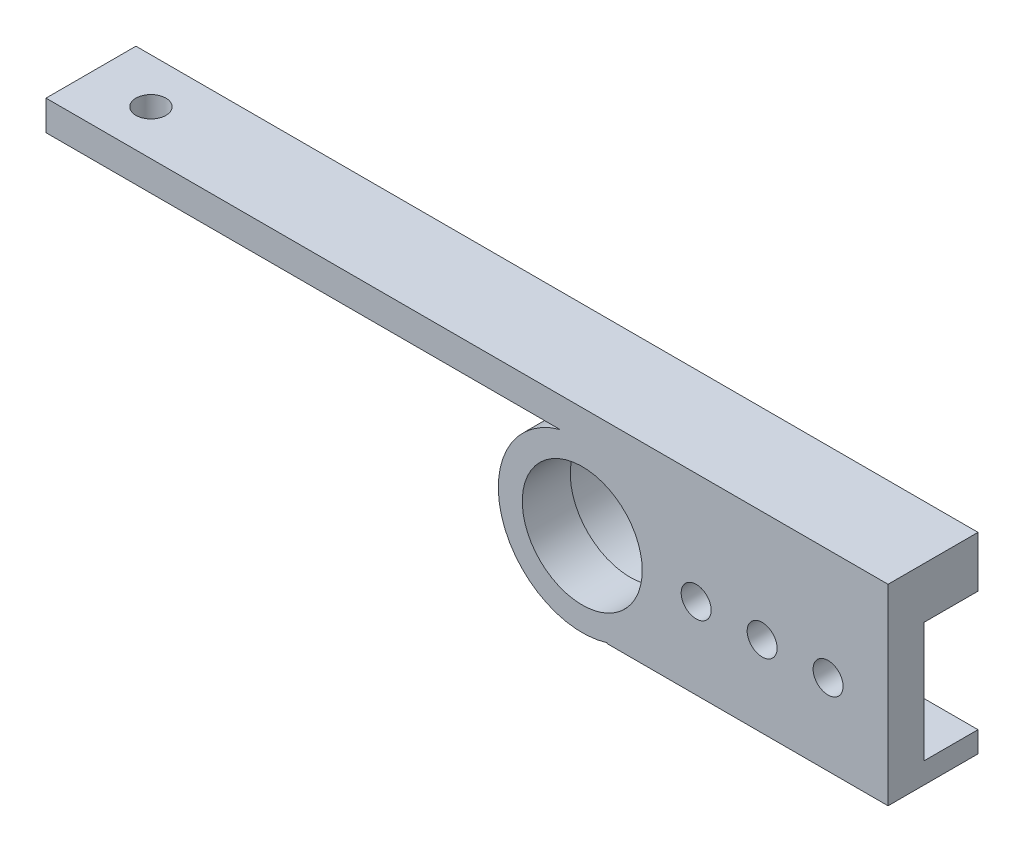
SolidWorks part; units mm, degrees
ref_plane "前视基准面" through (0, 0, 0) normal (0, 0, 1) x (1, 0, 0)
ref_plane "上视基准面" through (0, 0, 0) normal (0, 1, 0) x (1, 0, 0)
ref_plane "右视基准面" through (0, 0, 0) normal (1, 0, 0) x (0, 0, -1)
sketch "草图1" plane through (0, 0, 0) normal (0, 0, 1) x (1, 0, 0)
  line L1 (20, -10) -> (-20, -10)
  line L2 (20, -10) -> (20, 10)
  line L3 (20, 10) -> (-20, 10)
  line L4 (-20, -10) -> (-20, 10)
  line L5 (20, -10) -> (-20, 10) construction
  line L6 (20, 10) -> (-20, -10) construction
  point P0 (0, 0)
  dimension "D1" = 40
  dimension "D2" = 20
extrude "凸台-拉伸1" add sketch "草图1" along normal blind 6
sketch "草图2" plane through (0, 0, 6) normal (0, 0, 1) x (1, 0, 0)
  line L0 (20, -10) -> (20, 10) construction
  circle A0 centre (10, 0) radius 2.5
  circle A1 centre (-1, 0) radius 2.5
  circle A2 centre (-12, 0) radius 2.5
  dimension "D1" = 10
  dimension "D2" = 5
  dimension "D3" = 3
extrude "切除-拉伸1" cut sketch "草图2" against normal through all
sketch "草图3" plane through (0, 0, 6) normal (0, 0, 1) x (1, 0, 0)
  line L0 (20, 13.5) -> (20, 10)
  line L1 (20, -13.5) -> (-26.894, -13.5)
  line L3 (20, 13.5) -> (-26.894, 13.5)
  line L4 (-20, 10) -> (-20, -10)
  line L5 (-20, -10) -> (20, -10)
  line L6 (20, -10) -> (20, 10)
  line L7 (20, 10) -> (-20, 10)
  line L8 (-20, 10) -> (-20, -10)
  line L9 (-20, -10) -> (20, -10)
  line L10 (20, -10) -> (20, 10)
  line L11 (20, 10) -> (-20, 10)
  line L12 (-26.894, -13.5) -> (-26.894, 13.5)
  line L13 (20, -10.0394) -> (-26.894, 13.5) construction
  line L14 (20, 10.0394) -> (-26.894, -13.5) construction
  line L15 (20, -10) -> (20, -13.5)
  circle A0 centre (-31, 0) radius 11
  circle A1 centre (-31, 0) radius 14
  point P2 (0, 0)
  line M10 (-20, 10) -> (-20, -10)
  line M11 (-20, -10) -> (20, -10)
  line M13 (20, 10) -> (-20, 10)
  dimension "D3" = 22
  dimension "D4" = 28
  dimension "D2" = 3.5
  dimension "D1" = 0
extrude "凸台-拉伸2" add sketch "草图3" against normal blind 15 contours L3 A1 L1 L12 A0 | A1 L1 L15 M11 M10 | L1 A1 L8 A0 L12 | L8 A1 L3 L12 A0 | L8 A1 | A1 L0 L3 M10 M13 region at (-1.9449, 11.7771, 6) region at (-1.9449, -11.7771, 6) region at (-23.0173, 9.0328, 6) region at (-27.2274, 11.7946, 6) region at (-18.7882, 0, 6) region at (-23.0173, -9.0328, 6)
sketch "草图5" plane through (0, 0, 6) normal (0, 0, 1) x (1, 0, 0)
  circle A0 centre (-31, 0) radius 10
  circle A1 centre (-31, 0) radius 11 construction
  circle A2 centre (-31, 0) radius 11
  dimension "D1" = 20
extrude "凸台-拉伸3" add sketch "草图5" against normal blind 8
sketch "草图6" plane through (0, 0, 6) normal (0, 0, 1) x (1, 0, 0)
  circle A0 centre (-31, 0) radius 8.5
  circle A1 centre (-31, 0) radius 10 construction
  circle A2 centre (-31, 0) radius 10
  dimension "D1" = 17
sketch "草图7" plane through (0, 13.5, 0) normal (0, 1, 0) x (1, 0, 0)
  circle A0 centre (-16.8213, 3.0525) radius 3.3366
sketch "草图8" plane through (20, 0, 0) normal (1, 0, 0) x (0, 0, -1)
  line L1 (-6, 13.5) -> (9, 13.5)
  line L2 (-6, 13.5) -> (-6, 18.5)
  line L3 (-6, 18.5) -> (9, 18.5)
  line L4 (9, 13.5) -> (9, 18.5)
  dimension "D1" = 5
extrude "凸台-拉伸4" add sketch "草图8" against normal blind 140.43
sketch "草图9" plane through (0, 0, 6) normal (0, 0, 1) x (1, 0, 0)
  line L1 (-29.5663, 15.6648) -> (-25.1627, 15.6648)
  line L2 (-29.5663, 15.6648) -> (-29.5663, 11.9284)
  line L3 (-29.5663, 11.9284) -> (-25.1627, 11.9284)
  line L4 (-25.1627, 15.6648) -> (-25.1627, 11.9284)
extrude "凸台-拉伸5" add sketch "草图9" against normal through all
sketch "草图10" plane through (0, 18.5, 0) normal (0, 1, 0) x (1, 0, 0)
  line L0 (-120.43, 1.5) -> (-110.43, 1.5) construction
  line L1 (-120.43, 9) -> (-120.43, -6) construction
  circle A0 centre (-110.43, 1.5) radius 2.5
  dimension "D1" = 5
  dimension "D2" = 10
extrude "切除-拉伸2" cut sketch "草图10" against normal blind 10
